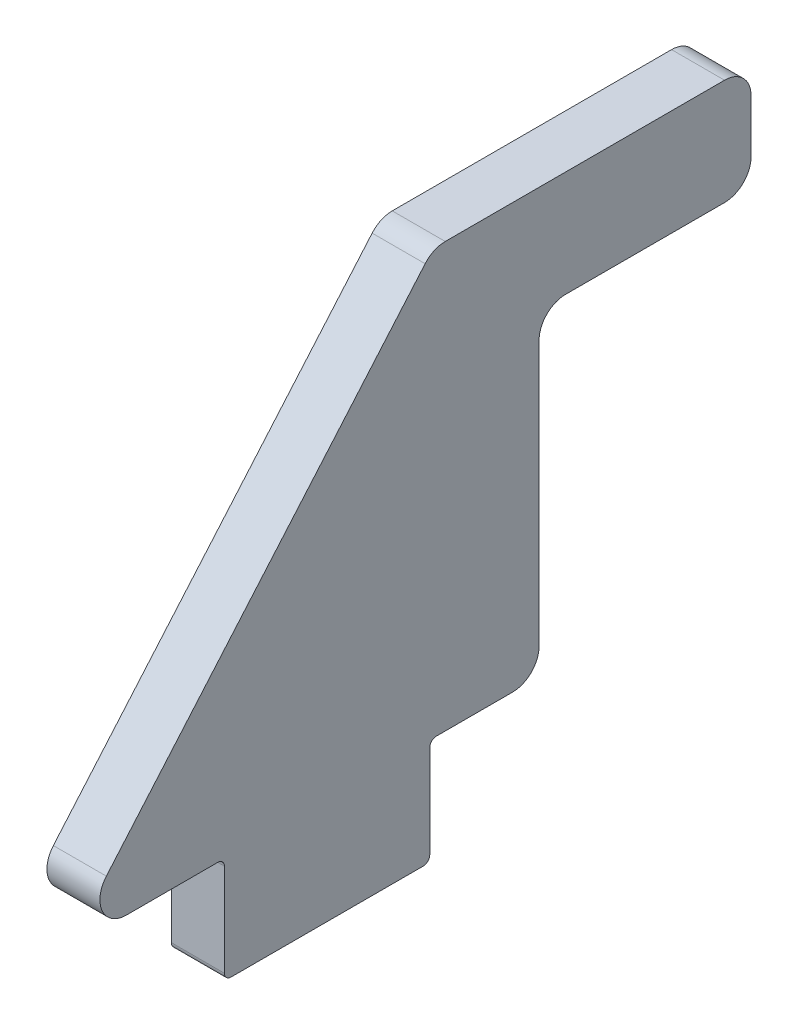
SolidWorks part; units mm, degrees
material "Plain Carbon Steel"
ref_plane "Front" through (0, 0, 0) normal (0, 0, 1) x (1, 0, 0)
ref_plane "Top" through (0, 0, 0) normal (0, 1, 0) x (1, 0, 0)
ref_plane "Right" through (0, 0, 0) normal (1, 0, 0) x (0, 0, -1)
sketch "Sketch1" plane through (0, 0, 0) normal (1, 0, 0) x (0, 0, -1)
  line L0 (-56.3562, 0) -> (-12.7, 50.8)
  line L2 (25.4, 38.1) -> (0, 38.1)
  line L3 (0, 38.1) -> (0, 0)
  line L4 (0, 0) -> (-13.0969, 0)
  line L5 (-13.0969, 0) -> (-13.0969, -12.7)
  line L6 (-13.0969, -12.7) -> (-37.7031, -12.7)
  line L7 (-37.7031, -12.7) -> (-37.7031, 0)
  line L8 (-37.7031, 0) -> (-56.3562, 0)
  line L9 (-12.7, 50.8) -> (25.4, 50.8)
  line L10 (25.4, 50.8) -> (25.4, 38.1)
  dimension "D1" = 25.4
  dimension "D2" = 38.1
  dimension "D3" = 24.6062
  dimension "D4" = 12.7
  dimension "D5" = 18.6531
  dimension "D6" = 12.7
  dimension "D7" = 38.1
  dimension "D8" = 13.0969
  dimension "D9" = 12.7
base flange "Base-Flange1" sketch "Sketch1" thickness 6.35 reverse thickness direction no parameters "D1"=7.9502
fillet "Fillet1" radius 3.175 6 edges at (-3.175, 0, 0) (-3.175, 38.1, 0) (-3.175, 38.1, -25.4) (-3.175, 50.8, -25.4) (-3.175, 0, 56.3562) (-3.175, 50.8, 12.7)
fillet "Fillet2" radius 0.7937 4 edges at (-3.175, 0, 13.0969) (-3.175, -12.7, 13.0969) (-3.175, -12.7, 37.7031) (-3.175, 0, 37.7031)
sketch "Bend-Lines1" [suppressed] plane through (0, 0, 0) normal (0, 1, 0) x (1, 0, 0)
sketch "Bounding-Box1" [suppressed] plane through (0, 0, 0) normal (0, 1, 0) x (1, 0, 0)
sheet metal parameters "Sheet-Metal28" thickness 6.35 parameters "D1"=15.621
flat pattern "Flat-Pattern28" [suppressed]
sketch "Bend-Lines2" plane through (0, 0, 0) normal (0, 1, 0) x (1, 0, 0)
sketch3d "Bounding-Box2" [suppressed]
  line L0 (-23.0696, -24.8462, 0) -> (34.0642, 41.6368, 0) construction
  line L1 (-54.4979, 2.1625, 0) -> (2.6359, 68.6455, 0) construction
  line L2 (-23.0696, -24.8462, 0) -> (-54.4979, 2.1625, 0) construction
  line L3 (34.0642, 41.6368, 0) -> (2.6359, 68.6455, 0) construction
equation "\"Total Cutting Length\"= \"Cutting Length-Outer\" + \"Cutting Length-Inner\""
equation "\"Amount in ft^2\"= \"Bounding Box Area-Blank\" / 144"
